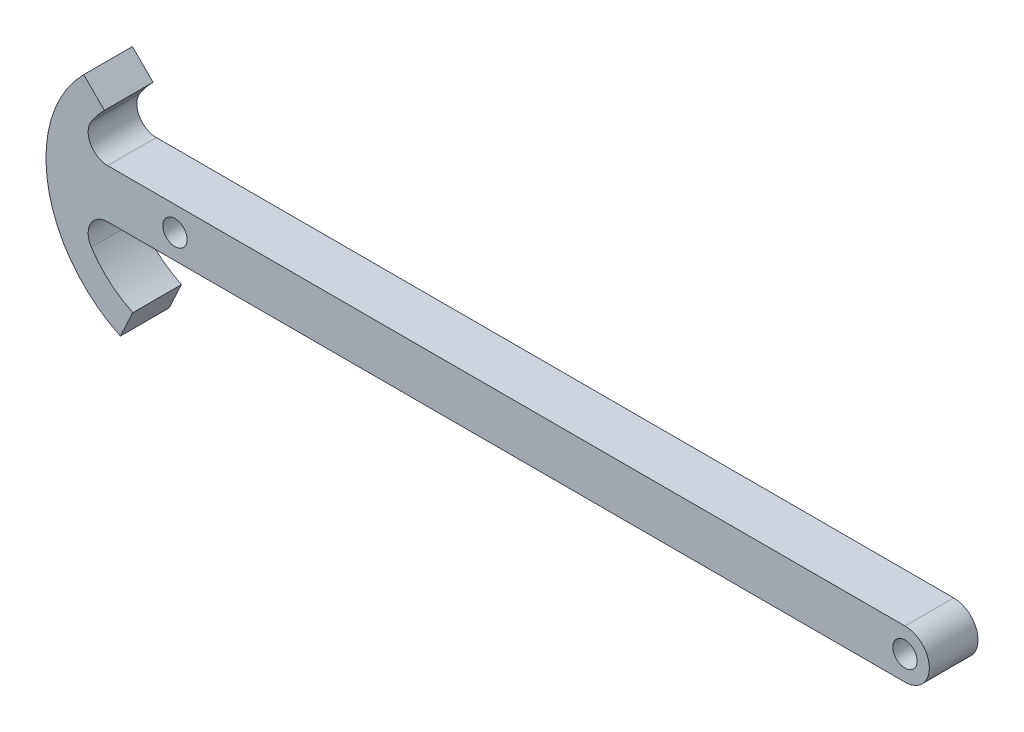
SolidWorks part; units mm, degrees
ref_plane "Front Plane" through (0, 0, 0) normal (0, 0, 1) x (1, 0, 0)
ref_plane "Top Plane" through (0, 0, 0) normal (0, 1, 0) x (1, 0, 0)
ref_plane "Right Plane" through (0, 0, 0) normal (1, 0, 0) x (0, 0, -1)
ref_axis "X" through (-88.99, 0, 0) along (1, 0, 0)
ref_axis "Y" through (0, 55, 0) along (0, -1, 0)
ref_axis "Z" through (0, 0, -88.99) along (0, 0, 1)
sketch "Sketch1" plane through (0, 0, 0) normal (0, 0, 1) x (1, 0, 0)
  line L0 (0, 0) -> (150, 0) construction
  line L1 (0, 5) -> (150, 5)
  line L2 (0, -5) -> (150, -5)
  arc A0 (0, 5) -> (0, -5) centre (0, 0) ccw
  arc A1 (150, -5) -> (150, 5) centre (150, 0) ccw
  circle A2 centre (0, 0) radius 2.5
  circle A3 centre (150, 0) radius 2.5
  point P3 (75, 0)
  dimension "D1" = 5
  dimension "D3" = 5
  dimension "D2" = 150
extrude "Boss-Extrude1" add sketch "Sketch1" along normal mid plane 10
sketch "Sketch2" plane through (0, 0, 0) normal (0, 0, 1) x (1, 0, 0)
  line L0 (0, 5) -> (-19.8809, 5)
  line L1 (0, -5) -> (-19.8809, -5)
  line L2 (0, 0) -> (-14.4957, 14.4957) construction
  line L3 (0, 0) -> (-8.6637, -18.5793) construction
  line L4 (0, 0) -> (150, 0) construction
  line L5 (-14.4957, 14.4957) -> (-18.7383, 18.7383)
  line L6 (-8.6637, -18.5793) -> (-11.1994, -24.0172)
  arc A0 (-19.8809, 5) -> (-14.4957, 14.4957) centre (0, 0) cw
  arc A1 (-19.8809, -5) -> (-8.6637, -18.5793) centre (0, 0) ccw
  arc A3 (-18.7383, 18.7383) -> (-11.1994, -24.0172) centre (0, 0) ccw
  arc A4 (0, 5) -> (0, -5) centre (0, 0) ccw construction
  arc A5 (0, 5) -> (0, -5) centre (0, 0) ccw
  point P10 (-21.0691, 5)
  point P15 (-18.967, -18.6965)
  dimension "D1" = 135
  dimension "D3" = 20.5
  dimension "D2" = 110
  dimension "D4" = 6
extrude "Boss-Extrude2" add sketch "Sketch2" along normal up to surface and the other way up to surface up to face at (2.5, 0, 5) other way up to face at (75, 0, -5)
fillet "Fillet1" radius 4 2 edges at (-19.8809, 5, 0) (-19.8809, -5, 0)
